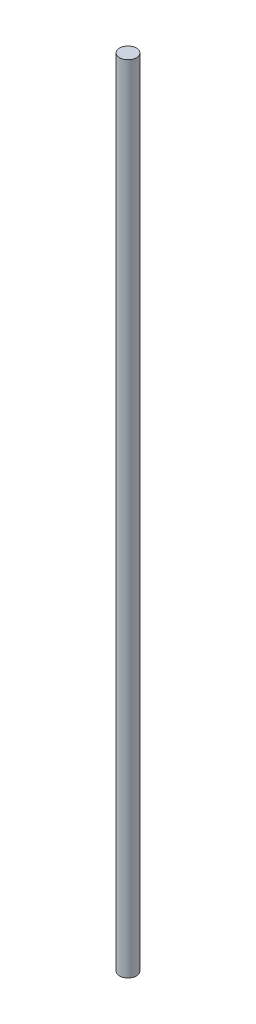
SolidWorks part; units mm, degrees
ref_plane "Front Plane" through (0, 0, 0) normal (0, 0, 1) x (1, 0, 0)
ref_plane "Top Plane" through (0, 0, 0) normal (0, 1, 0) x (1, 0, 0)
ref_plane "Right Plane" through (0, 0, 0) normal (1, 0, 0) x (0, 0, -1)
ref_axis "X" through (-88.99, 0, 0) along (1, 0, 0)
ref_axis "Y" through (0, 55, 0) along (0, -1, 0)
ref_axis "Z" through (0, 0, -88.99) along (0, 0, 1)
sketch "Sketch1" plane through (0, 0, 0) normal (0, 1, 0) x (1, 0, 0)
  circle A0 centre (0, 0) radius 0.7937
  dimension "D1" = 1.5875
extrude "Boss-Extrude1" add sketch "Sketch1" along normal blind 75
